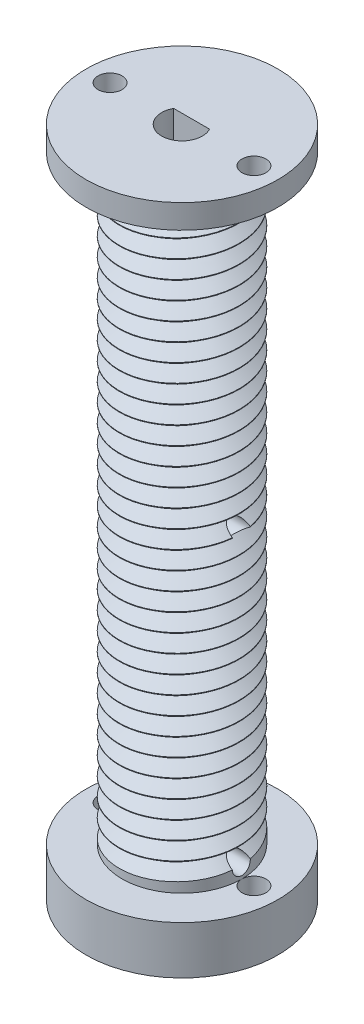
SolidWorks part; units mm, degrees
note: The reader was unsure of these and kept them because the rebuilt part matched: shared geometry of "Esboço2<2>", "Esboço101<2>", "Esboço8<3>", "Esboço49<3>".
ref_plane "Plano frontal" through (0, 0, 0) normal (0, 0, 1) x (1, 0, 0)
ref_plane "Plano superior" through (0, 0, 0) normal (0, 1, 0) x (1, 0, 0)
ref_plane "Plano direito" through (0, 0, 0) normal (1, 0, 0) x (0, 0, -1)
sketch "Esboço2" plane through (0, 0, 0) normal (0, 1, 0) x (1, 0, 0)
  circle A0 centre (0, 0) radius 5
  dimension "D1" = 10
curve "Hélice/Espiral1" pitch 1.5 height 24 turns 16
extrude "Ressalto-extrusão2" add sketch "Esboço2<2>" along normal mid plane 50
sketch "Esboço2<2>" plane through (0, 0, 0) normal (0, 1, 0) x (1, 0, 0) same geometry as "Esboço2"
sketch "Esboço101" plane through (0, 0, 0) normal (0, 0, 1) x (1, 0, 0)
  line L0 (-5, 0.725) -> (-4, 0)
  line L1 (-5, 25) -> (-5, -25) construction
  line L2 (-4, 0) -> (-5, -0.725)
  line L3 (-5, -0.725) -> (-5, 0.725)
  dimension "D1" = 1.45
  dimension "D2" = 1
  dimension "D3" = 71.884
sweep "Varredura de corte1" cut profiles "Esboço101" path "Hélice/Espiral1" align with end faces yes
sketch "Esboço8" plane through (0, 25, 0) normal (0, 1, 0) x (1, 0, 0)
  line L0 (0, 0) -> (0, 3.3538) construction
  circle A0 centre (0, 0) radius 8
  circle A1 centre (6, 0) radius 1
  circle A4 centre (0, 0) radius 5 construction
  circle A5 centre (-6, 0) radius 1
  dimension "D1" = 3
  dimension "D2" = 2
  dimension "D3" = 2
extrude "Ressalto-extrusão3" add sketch "Esboço8" along normal blind 2
sketch "Esboço10" plane through (0, 0, 0) normal (0, 1, 0) x (1, 0, 0)
  circle A0 centre (0, 0) radius 5 construction
  circle A1 centre (0, 0) radius 5
curve "Hélice/Espiral2" pitch 1.5 height 24 turns 16
sweep "Varredura de corte6" cut profiles "Esboço101<2>" path "Hélice/Espiral2" align with end faces yes
sketch "Esboço101<2>" plane through (0, 0, 0) normal (0, 0, 1) x (1, 0, 0) same geometry as "Esboço101"
extrude "Ressalto-extrusão5" add sketch "Esboço8<3>" against normal blind 4 from surface at -50 starting at face at (0, -25, 5)
sketch "Esboço8<3>" plane through (0, 25, 0) normal (0, 1, 0) x (1, 0, 0) same geometry as "Esboço8"
sketch "Esboço48" plane through (0, 0, 0) normal (0, 1, 0) x (1, 0, 0)
  line L0 (-1.5, 0.8) -> (1.5, 0.8)
  arc A0 (-1.5, 0.8) -> (1.5, 0.8) centre (0, 0) ccw
  dimension "D1" = 3.4
  dimension "D2" = 2.5
extrude "Corte-extrusão1" cut sketch "Esboço48" against normal through all both and the other way through all
sketch "Esboço49" plane through (0, 0, 0) normal (0, 0, 1) x (1, 0, 0)
  line L0 (-8, -25) -> (8, -29) construction
  line L1 (0, 0) -> (-2.9716, 0) construction
  circle A1 centre (0, -27) radius 0.8
  circle A2 centre (0, -27) radius 1.3
  dimension "D1" = 1.6
  dimension "D2" = 2.6
extrude "Corte-extrusão2" cut sketch "Esboço49" against normal through all contours A1
extrude "Corte-extrusão3" cut sketch "Esboço49<3>" against normal blind 12 from offset 4 offset against normal yes
sketch "Esboço49<3>" plane through (0, 0, 0) normal (0, 0, 1) x (1, 0, 0) same geometry as "Esboço49"
sketch "Esboço103" plane through (0, 0, 0) normal (1, 0, 0) x (0, 0, -1)
  line L0 (0, -23.275) -> (0, -24.725) construction
  circle A0 centre (0, 0) radius 0.75
  circle A1 centre (0.2427, 23.9861) radius 0.75
  circle A2 centre (0, -24) radius 0.75
  spline S0 degree 2 poles (0, 0.725) (-2.0711, 0.8188) (-3.5355, 0.9125) (-5, 1.0063) (-5, 1.1) (-5, 1.1937) (-3.5355, 1.2875) (-2.0711, 1.3813) (0, 1.475) (2.0711, 1.5687) (3.5355, 1.6625) (5, 1.7563) (5, 1.85) (5, 1.9437) (3.5355, 2.0375) (2.0711, 2.1313) (0, 2.225) (-2.0711, 2.3188) (-3.5355, 2.4125) (-5, 2.5062) (-5, 2.6) (-5, 2.6938) (-3.5355, 2.7875) (-2.0711, 2.8813) (0, 2.975) (2.0711, 3.0687) (3.5355, 3.1625) (5, 3.2563) (5, 3.35) (5, 3.4438) (3.5355, 3.5375) (2.0711, 3.6313) (0, 3.725) (-2.0711, 3.8188) (-3.5355, 3.9125) (-5, 4.0062) (-5, 4.1) (-5, 4.1937) (-3.5355, 4.2875) (-2.0711, 4.3813) (0, 4.475) (2.0711, 4.5688) (3.5355, 4.6625) (5, 4.7562) (5, 4.85) (5, 4.9438) (3.5355, 5.0375) (2.0711, 5.1313) (0, 5.225) (-2.0711, 5.3187) (-3.5355, 5.4125) (-5, 5.5062) (-5, 5.6) (-5, 5.6937) (-3.5355, 5.7875) (-2.0711, 5.8813) (0, 5.975) (2.0711, 6.0688) (3.5355, 6.1625) (5, 6.2562) (5, 6.35) (5, 6.4437) (3.5355, 6.5375) (2.0711, 6.6312) (0, 6.725) (-2.0711, 6.8188) (-3.5355, 6.9125) (-5, 7.0063) (-5, 7.1) (-5, 7.1938) (-3.5355, 7.2875) (-2.0711, 7.3812) (0, 7.475) (2.0711, 7.5687) (3.5355, 7.6625) (5, 7.7563) (5, 7.85) (5, 7.9437) (3.5355, 8.0375) (2.0711, 8.1312) (0, 8.225) (-2.0711, 8.3187) (-3.5355, 8.4125) (-5, 8.5063) (-5, 8.6) (-5, 8.6937) (-3.5355, 8.7875) (-2.0711, 8.8813) (0, 8.975) (2.0711, 9.0687) (3.5355, 9.1625) (5, 9.2563) (5, 9.35) (5, 9.4438) (3.5355, 9.5375) (2.0711, 9.6313) (0, 9.725) (-2.0711, 9.8187) (-3.5355, 9.9125) (-5, 10.0062) (-5, 10.1) (-5, 10.1937) (-3.5355, 10.2875) (-2.0711, 10.3812) (0, 10.475) (2.0711, 10.5687) (3.5355, 10.6625) (5, 10.7562) (5, 10.85) (5, 10.9437) (3.5355, 11.0375) (2.0711, 11.1312) (0, 11.225) (-2.0711, 11.3188) (-3.5355, 11.4125) (-5, 11.5063) (-5, 11.6) (-5, 11.6938) (-3.5355, 11.7875) (-2.0711, 11.8812) (0, 11.975) (2.0711, 12.0687) (3.5355, 12.1625) (5, 12.2562) (5, 12.35) (5, 12.4437) (3.5355, 12.5375) (2.0711, 12.6312) (0, 12.725) (-2.0711, 12.8187) (-3.5355, 12.9125) (-5, 13.0062) (-5, 13.1) (-5, 13.1938) (-3.5355, 13.2875) (-2.0711, 13.3813) (0, 13.475) (2.0711, 13.5688) (3.5355, 13.6625) (5, 13.7562) (5, 13.85) (5, 13.9437) (3.5355, 14.0375) (2.0711, 14.1312) (0, 14.225) (-2.0711, 14.3187) (-3.5355, 14.4125) (-5, 14.5062) (-5, 14.6) (-5, 14.6937) (-3.5355, 14.7875) (-2.0711, 14.8812) (0, 14.975) (2.0711, 15.0688) (3.5355, 15.1625) (5, 15.2563) (5, 15.35) (5, 15.4438) (3.5355, 15.5375) (2.0711, 15.6312) (0, 15.725) (-2.0711, 15.8187) (-3.5355, 15.9125) (-5, 16.0063) (-5, 16.1) (-5, 16.1938) (-3.5355, 16.2875) (-2.0711, 16.3813) (0, 16.475) (2.0711, 16.5688) (3.5355, 16.6625) (5, 16.7563) (5, 16.85) (5, 16.9438) (3.5355, 17.0375) (2.0711, 17.1313) (0, 17.225) (-2.0711, 17.3188) (-3.5355, 17.4125) (-5, 17.5063) (-5, 17.6) (-5, 17.6938) (-3.5355, 17.7875) (-2.0711, 17.8813) (0, 17.975) (2.0711, 18.0688) (3.5355, 18.1625) (5, 18.2563) (5, 18.35) (5, 18.4438) (3.5355, 18.5375) (2.0711, 18.6313) (0, 18.725) (-2.0711, 18.8187) (-3.5355, 18.9125) (-5, 19.0063) (-5, 19.1) (-5, 19.1937) (-3.5355, 19.2875) (-2.0711, 19.3812) (0, 19.475) (2.0711, 19.5687) (3.5355, 19.6625) (5, 19.7563) (5, 19.85) (5, 19.9438) (3.5355, 20.0375) (2.0711, 20.1313) (0, 20.225) (-2.0711, 20.3188) (-3.5355, 20.4125) (-5, 20.5063) (-5, 20.6) (-5, 20.6938) (-3.5355, 20.7875) (-2.0711, 20.8813) (0, 20.975) (2.0711, 21.0688) (3.5355, 21.1625) (5, 21.2563) (5, 21.35) (5, 21.4438) (3.5355, 21.5375) (2.0711, 21.6313) (0, 21.725) (-2.0711, 21.8188) (-3.5355, 21.9125) (-5, 22.0063) (-5, 22.1) (-5, 22.1938) (-3.5355, 22.2875) (-2.0711, 22.3813) (0, 22.475) (2.0711, 22.5688) (3.5355, 22.6625) (5, 22.7562) (5, 22.85) (5, 22.9438) (3.5355, 23.0375) (2.0711, 23.1312) (0, 23.225) (-2.0711, 23.3187) (-3.5355, 23.4125) (-5, 23.5062) (-5, 23.6) (-5, 23.6938) (-3.5355, 23.7875) (-2.0711, 23.8813) (0, 23.975) (2.0711, 24.0688) (3.5355, 24.1625) (5, 24.2563) (5, 24.35) (5, 24.4438) (3.5355, 24.5375) (2.0711, 24.6313) (0, 24.725) knots 0 0 0 0.007812 0.007812 0.015625 0.015625 0.023438 0.023438 0.03125 0.03125 0.039062 0.039062 0.046875 0.046875 0.054688 0.054688 0.0625 0.0625 0.070312 0.070312 0.078125 0.078125 0.085938 0.085938 0.09375 0.09375 0.101562 0.101562 0.109375 0.109375 0.117188 0.117188 0.125 0.125 0.132812 0.132812 0.140625 0.140625 0.148438 0.148438 0.15625 0.15625 0.164062 0.164062 0.171875 0.171875 0.179688 0.179688 0.1875 0.1875 0.195312 0.195312 0.203125 0.203125 0.210938 0.210938 0.21875 0.21875 0.226562 0.226562 0.234375 0.234375 0.242188 0.242188 0.25 0.25 0.257812 0.257812 0.265625 0.265625 0.273438 0.273438 0.28125 0.28125 0.289062 0.289062 0.296875 0.296875 0.304688 0.304688 0.3125 0.3125 0.320312 0.320312 0.328125 0.328125 0.335938 0.335938 0.34375 0.34375 0.351562 0.351562 0.359375 0.359375 0.367188 0.367188 0.375 0.375 0.382812 0.382812 0.390625 0.390625 0.398438 0.398438 0.40625 0.40625 0.414062 0.414062 0.421875 0.421875 0.429688 0.429688 0.4375 0.4375 0.445312 0.445312 0.453125 0.453125 0.460938 0.460938 0.46875 0.46875 0.476562 0.476562 0.484375 0.484375 0.492188 0.492188 0.5 0.5 0.507812 0.507812 0.515625 0.515625 0.523438 0.523438 0.53125 0.53125 0.539062 0.539062 0.546875 0.546875 0.554688 0.554688 0.5625 0.5625 0.570312 0.570312 0.578125 0.578125 0.585938 0.585938 0.59375 0.59375 0.601562 0.601562 0.609375 0.609375 0.617188 0.617188 0.625 0.625 0.632812 0.632812 0.640625 0.640625 0.648438 0.648438 0.65625 0.65625 0.664062 0.664062 0.671875 0.671875 0.679688 0.679688 0.6875 0.6875 0.695312 0.695312 0.703125 0.703125 0.710938 0.710938 0.71875 0.71875 0.726562 0.726562 0.734375 0.734375 0.742188 0.742188 0.75 0.75 0.757812 0.757812 0.765625 0.765625 0.773438 0.773438 0.78125 0.78125 0.789062 0.789062 0.796875 0.796875 0.804688 0.804688 0.8125 0.8125 0.820312 0.820312 0.828125 0.828125 0.835938 0.835938 0.84375 0.84375 0.851562 0.851562 0.859375 0.859375 0.867188 0.867188 0.875 0.875 0.882812 0.882812 0.890625 0.890625 0.898438 0.898438 0.90625 0.90625 0.914062 0.914062 0.921875 0.921875 0.929688 0.929688 0.9375 0.9375 0.945312 0.945312 0.953125 0.953125 0.960938 0.960938 0.96875 0.96875 0.976562 0.976562 0.984375 0.984375 0.992188 0.992188 1 1 1 weights 1 0.92388 1 0.92388 1 0.92388 1 0.92388 1 0.92388 1 0.92388 1 0.92388 1 0.92388 1 0.92388 1 0.92388 1 0.92388 1 0.92388 1 0.92388 1 0.92388 1 0.92388 1 0.92388 1 0.92388 1 0.92388 1 0.92388 1 0.92388 1 0.92388 1 0.92388 1 0.92388 1 0.92388 1 0.92388 1 0.92388 1 0.92388 1 0.92388 1 0.92388 1 0.92388 1 0.92388 1 0.92388 1 0.92388 1 0.92388 1 0.92388 1 0.92388 1 0.92388 1 0.92388 1 0.92388 1 0.92388 1 0.92388 1 0.92388 1 0.92388 1 0.92388 1 0.92388 1 0.92388 1 0.92388 1 0.92388 1 0.92388 1 0.92388 1 0.92388 1 0.92388 1 0.92388 1 0.92388 1 0.92388 1 0.92388 1 0.92388 1 0.92388 1 0.92388 1 0.92388 1 0.92388 1 0.92388 1 0.92388 1 0.92388 1 0.92388 1 0.92388 1 0.92388 1 0.92388 1 0.92388 1 0.92388 1 0.92388 1 0.92388 1 0.92388 1 0.92388 1 0.92388 1 0.92388 1 0.92388 1 0.92388 1 0.92388 1 0.92388 1 0.92388 1 0.92388 1 0.92388 1 0.92388 1 0.92388 1 0.92388 1 0.92388 1 0.92388 1 0.92388 1 0.92388 1 0.92388 1 0.92388 1 0.92388 1 0.92388 1 0.92388 1 0.92388 1 0.92388 1 0.92388 1 0.92388 1 0.92388 1 0.92388 1 0.92388 1 0.92388 1 0.92388 1 0.92388 1 0.92388 1 0.92388 1 0.92388 1 0.92388 1 0.92388 1 0.92388 1 0.92388 1 0.92388 1 0.92388 1 0.92388 1 0.92388 1 0.92388 1 0.92388 1 0.92388 1 0.92388 1 0.92388 1 0.92388 1 0.92388 1 0.92388 1 0.92388 1 0.92388 1 0.92388 1 0.92388 1 construction
  spline S1 degree 2 poles (0, 0) (-1.6569, 0.0938) (-2.8284, 0.1875) (-4, 0.2813) (-4, 0.375) (-4, 0.4688) (-2.8284, 0.5625) (-1.6569, 0.6563) (0, 0.75) (1.6569, 0.8438) (2.8284, 0.9375) (4, 1.0312) (4, 1.125) (4, 1.2188) (2.8284, 1.3125) (1.6569, 1.4062) (0, 1.5) (-1.6569, 1.5938) (-2.8284, 1.6875) (-4, 1.7812) (-4, 1.875) (-4, 1.9688) (-2.8284, 2.0625) (-1.6569, 2.1563) (0, 2.25) (1.6569, 2.3438) (2.8284, 2.4375) (4, 2.5313) (4, 2.625) (4, 2.7188) (2.8284, 2.8125) (1.6569, 2.9062) (0, 3) (-1.6569, 3.0938) (-2.8284, 3.1875) (-4, 3.2812) (-4, 3.375) (-4, 3.4688) (-2.8284, 3.5625) (-1.6569, 3.6562) (0, 3.75) (1.6569, 3.8438) (2.8284, 3.9375) (4, 4.0312) (4, 4.125) (4, 4.2188) (2.8284, 4.3125) (1.6569, 4.4062) (0, 4.5) (-1.6569, 4.5938) (-2.8284, 4.6875) (-4, 4.7812) (-4, 4.875) (-4, 4.9688) (-2.8284, 5.0625) (-1.6569, 5.1562) (0, 5.25) (1.6569, 5.3438) (2.8284, 5.4375) (4, 5.5312) (4, 5.625) (4, 5.7188) (2.8284, 5.8125) (1.6569, 5.9062) (0, 6) (-1.6569, 6.0938) (-2.8284, 6.1875) (-4, 6.2812) (-4, 6.375) (-4, 6.4688) (-2.8284, 6.5625) (-1.6569, 6.6562) (0, 6.75) (1.6569, 6.8438) (2.8284, 6.9375) (4, 7.0312) (4, 7.125) (4, 7.2188) (2.8284, 7.3125) (1.6569, 7.4063) (0, 7.5) (-1.6569, 7.5938) (-2.8284, 7.6875) (-4, 7.7812) (-4, 7.875) (-4, 7.9688) (-2.8284, 8.0625) (-1.6569, 8.1562) (0, 8.25) (1.6569, 8.3438) (2.8284, 8.4375) (4, 8.5312) (4, 8.625) (4, 8.7188) (2.8284, 8.8125) (1.6569, 8.9063) (0, 9) (-1.6569, 9.0938) (-2.8284, 9.1875) (-4, 9.2812) (-4, 9.375) (-4, 9.4688) (-2.8284, 9.5625) (-1.6569, 9.6562) (0, 9.75) (1.6569, 9.8438) (2.8284, 9.9375) (4, 10.0312) (4, 10.125) (4, 10.2188) (2.8284, 10.3125) (1.6569, 10.4062) (0, 10.5) (-1.6569, 10.5938) (-2.8284, 10.6875) (-4, 10.7813) (-4, 10.875) (-4, 10.9688) (-2.8284, 11.0625) (-1.6569, 11.1562) (0, 11.25) (1.6569, 11.3438) (2.8284, 11.4375) (4, 11.5312) (4, 11.625) (4, 11.7188) (2.8284, 11.8125) (1.6569, 11.9062) (0, 12) (-1.6569, 12.0938) (-2.8284, 12.1875) (-4, 12.2812) (-4, 12.375) (-4, 12.4688) (-2.8284, 12.5625) (-1.6569, 12.6562) (0, 12.75) (1.6569, 12.8438) (2.8284, 12.9375) (4, 13.0312) (4, 13.125) (4, 13.2188) (2.8284, 13.3125) (1.6569, 13.4062) (0, 13.5) (-1.6569, 13.5938) (-2.8284, 13.6875) (-4, 13.7812) (-4, 13.875) (-4, 13.9688) (-2.8284, 14.0625) (-1.6569, 14.1562) (0, 14.25) (1.6569, 14.3438) (2.8284, 14.4375) (4, 14.5312) (4, 14.625) (4, 14.7188) (2.8284, 14.8125) (1.6569, 14.9063) (0, 15) (-1.6569, 15.0938) (-2.8284, 15.1875) (-4, 15.2812) (-4, 15.375) (-4, 15.4688) (-2.8284, 15.5625) (-1.6569, 15.6562) (0, 15.75) (1.6569, 15.8438) (2.8284, 15.9375) (4, 16.0312) (4, 16.125) (4, 16.2188) (2.8284, 16.3125) (1.6569, 16.4062) (0, 16.5) (-1.6569, 16.5938) (-2.8284, 16.6875) (-4, 16.7812) (-4, 16.875) (-4, 16.9688) (-2.8284, 17.0625) (-1.6569, 17.1562) (0, 17.25) (1.6569, 17.3438) (2.8284, 17.4375) (4, 17.5313) (4, 17.625) (4, 17.7188) (2.8284, 17.8125) (1.6569, 17.9063) (0, 18) (-1.6569, 18.0938) (-2.8284, 18.1875) (-4, 18.2812) (-4, 18.375) (-4, 18.4688) (-2.8284, 18.5625) (-1.6569, 18.6562) (0, 18.75) (1.6569, 18.8438) (2.8284, 18.9375) (4, 19.0312) (4, 19.125) (4, 19.2188) (2.8284, 19.3125) (1.6569, 19.4062) (0, 19.5) (-1.6569, 19.5938) (-2.8284, 19.6875) (-4, 19.7812) (-4, 19.875) (-4, 19.9688) (-2.8284, 20.0625) (-1.6569, 20.1562) (0, 20.25) (1.6569, 20.3438) (2.8284, 20.4375) (4, 20.5312) (4, 20.625) (4, 20.7188) (2.8284, 20.8125) (1.6569, 20.9062) (0, 21) (-1.6569, 21.0938) (-2.8284, 21.1875) (-4, 21.2812) (-4, 21.375) (-4, 21.4688) (-2.8284, 21.5625) (-1.6569, 21.6563) (0, 21.75) (1.6569, 21.8438) (2.8284, 21.9375) (4, 22.0312) (4, 22.125) (4, 22.2188) (2.8284, 22.3125) (1.6569, 22.4062) (0, 22.5) (-1.6569, 22.5938) (-2.8284, 22.6875) (-4, 22.7812) (-4, 22.875) (-4, 22.9688) (-2.8284, 23.0625) (-1.6569, 23.1562) (0, 23.25) (1.6569, 23.3438) (2.8284, 23.4375) (4, 23.5312) (4, 23.625) (4, 23.7188) (2.8284, 23.8125) (1.6569, 23.9062) (0, 24) knots 0 0 0 0.007812 0.007812 0.015625 0.015625 0.023438 0.023438 0.03125 0.03125 0.039062 0.039062 0.046875 0.046875 0.054688 0.054688 0.0625 0.0625 0.070312 0.070312 0.078125 0.078125 0.085938 0.085938 0.09375 0.09375 0.101562 0.101562 0.109375 0.109375 0.117188 0.117188 0.125 0.125 0.132812 0.132812 0.140625 0.140625 0.148438 0.148438 0.15625 0.15625 0.164062 0.164062 0.171875 0.171875 0.179688 0.179688 0.1875 0.1875 0.195312 0.195312 0.203125 0.203125 0.210938 0.210938 0.21875 0.21875 0.226562 0.226562 0.234375 0.234375 0.242188 0.242188 0.25 0.25 0.257812 0.257812 0.265625 0.265625 0.273438 0.273438 0.28125 0.28125 0.289062 0.289062 0.296875 0.296875 0.304688 0.304688 0.3125 0.3125 0.320312 0.320312 0.328125 0.328125 0.335938 0.335938 0.34375 0.34375 0.351562 0.351562 0.359375 0.359375 0.367188 0.367188 0.375 0.375 0.382812 0.382812 0.390625 0.390625 0.398438 0.398438 0.40625 0.40625 0.414062 0.414062 0.421875 0.421875 0.429688 0.429688 0.4375 0.4375 0.445312 0.445312 0.453125 0.453125 0.460938 0.460938 0.46875 0.46875 0.476562 0.476562 0.484375 0.484375 0.492188 0.492188 0.5 0.5 0.507812 0.507812 0.515625 0.515625 0.523438 0.523438 0.53125 0.53125 0.539062 0.539062 0.546875 0.546875 0.554688 0.554688 0.5625 0.5625 0.570312 0.570312 0.578125 0.578125 0.585938 0.585938 0.59375 0.59375 0.601562 0.601562 0.609375 0.609375 0.617188 0.617188 0.625 0.625 0.632812 0.632812 0.640625 0.640625 0.648438 0.648438 0.65625 0.65625 0.664062 0.664062 0.671875 0.671875 0.679688 0.679688 0.6875 0.6875 0.695312 0.695312 0.703125 0.703125 0.710938 0.710938 0.71875 0.71875 0.726562 0.726562 0.734375 0.734375 0.742188 0.742188 0.75 0.75 0.757812 0.757812 0.765625 0.765625 0.773438 0.773438 0.78125 0.78125 0.789062 0.789062 0.796875 0.796875 0.804688 0.804688 0.8125 0.8125 0.820312 0.820312 0.828125 0.828125 0.835938 0.835938 0.84375 0.84375 0.851562 0.851562 0.859375 0.859375 0.867188 0.867188 0.875 0.875 0.882812 0.882812 0.890625 0.890625 0.898438 0.898438 0.90625 0.90625 0.914062 0.914062 0.921875 0.921875 0.929688 0.929688 0.9375 0.9375 0.945312 0.945312 0.953125 0.953125 0.960938 0.960938 0.96875 0.96875 0.976562 0.976562 0.984375 0.984375 0.992188 0.992188 1 1 1 weights 1 0.92388 1 0.92388 1 0.92388 1 0.92388 1 0.92388 1 0.92388 1 0.92388 1 0.92388 1 0.92388 1 0.92388 1 0.92388 1 0.92388 1 0.92388 1 0.92388 1 0.92388 1 0.92388 1 0.92388 1 0.92388 1 0.92388 1 0.92388 1 0.92388 1 0.92388 1 0.92388 1 0.92388 1 0.92388 1 0.92388 1 0.92388 1 0.92388 1 0.92388 1 0.92388 1 0.92388 1 0.92388 1 0.92388 1 0.92388 1 0.92388 1 0.92388 1 0.92388 1 0.92388 1 0.92388 1 0.92388 1 0.92388 1 0.92388 1 0.92388 1 0.92388 1 0.92388 1 0.92388 1 0.92388 1 0.92388 1 0.92388 1 0.92388 1 0.92388 1 0.92388 1 0.92388 1 0.92388 1 0.92388 1 0.92388 1 0.92388 1 0.92388 1 0.92388 1 0.92388 1 0.92388 1 0.92388 1 0.92388 1 0.92388 1 0.92388 1 0.92388 1 0.92388 1 0.92388 1 0.92388 1 0.92388 1 0.92388 1 0.92388 1 0.92388 1 0.92388 1 0.92388 1 0.92388 1 0.92388 1 0.92388 1 0.92388 1 0.92388 1 0.92388 1 0.92388 1 0.92388 1 0.92388 1 0.92388 1 0.92388 1 0.92388 1 0.92388 1 0.92388 1 0.92388 1 0.92388 1 0.92388 1 0.92388 1 0.92388 1 0.92388 1 0.92388 1 0.92388 1 0.92388 1 0.92388 1 0.92388 1 0.92388 1 0.92388 1 0.92388 1 0.92388 1 0.92388 1 0.92388 1 0.92388 1 0.92388 1 0.92388 1 0.92388 1 0.92388 1 0.92388 1 0.92388 1 0.92388 1 0.92388 1 0.92388 1 0.92388 1 0.92388 1 0.92388 1 0.92388 1 0.92388 1 0.92388 1 0.92388 1 0.92388 1 0.92388 1 0.92388 1 0.92388 1 0.92388 1 construction
  point P11 (0, -24)
  point P13 (0, -24.725)
  dimension "D1" = 1.5
extrude "Corte-extrusão4" cut sketch "Esboço103" against normal through all both and the other way through all
